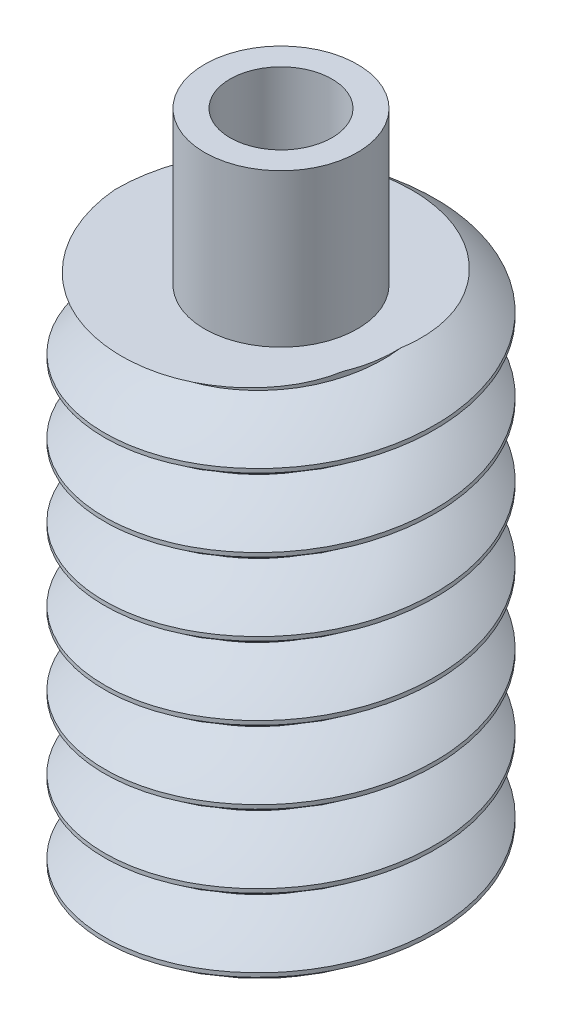
SolidWorks part; units mm, degrees
material "PE High Density"
ref_plane "Front Plane" through (0, 0, 0) normal (0, 0, 1) x (1, 0, 0)
ref_plane "Top Plane" through (0, 0, 0) normal (0, 1, 0) x (1, 0, 0)
ref_plane "Right Plane" through (0, 0, 0) normal (1, 0, 0) x (0, 0, -1)
sketch "Sketch1" plane through (0, 0, 0) normal (0, 1, 0) x (1, 0, 0)
  circle A0 centre (0, 0) radius 3.25
  dimension "D1" = 6.5
extrude "Boss-Extrude1" add sketch "Sketch1" along normal blind 10
sketch "Sketch2" plane through (0, 10, 0) normal (0, 1, 0) x (1, 0, 0)
  circle A1 centre (0, 0) radius 3.25
  circle A2 centre (0, 0) radius 3.25
  dimension "D1" = 0
curve "Helix/Spiral1" pitch 1.4286 height 10 turns 7
sketch "Sketch3" plane through (0, 0, 0) normal (0, 0, 1) x (1, 0, 0)
  line L0 (-3.25, 8.65) -> (-3.25, 10)
  line L1 (-2.25, 9.375) -> (-2.25, 9.275)
  line L2 (-3.25, 9.325) -> (-2.25, 9.325)
  arc A0 (-2.25, 9.275) -> (-3.25, 8.65) centre (-0.5149, 5.3863) ccw
  arc A1 (-2.25, 9.375) -> (-3.25, 10) centre (-0.5149, 13.2637) cw
  dimension "D1" = 0.675
  dimension "D2" = 0.05
  dimension "D3" = 1
sweep "Cut-Sweep1" cut profiles "Sketch3" path "Helix/Spiral1" align with end faces yes
sketch "Sketch4" plane through (0, 10, 0) normal (0, 1, 0) x (1, 0, 0)
  circle A0 centre (0, 0) radius 1.5
  dimension "D2" = 3
extrude "Cut-Extrude1" cut sketch "Sketch4" against normal through all contours A0
sketch "Sketch5" plane through (0, 10, 0) normal (0, 1, 0) x (1, 0, 0)
  circle A0 centre (0, 0) radius 1.5 construction
  circle A1 centre (0, 0) radius 1.5
extrude "Boss-Extrude3" add sketch "Sketch5" along normal blind 3 separate body
sketch "Sketch6" plane through (0, 13, 0) normal (0, 1, 0) x (1, 0, 0)
  circle A0 centre (0, 0) radius 1
extrude "Cut-Extrude2" cut sketch "Sketch6" against normal through all
